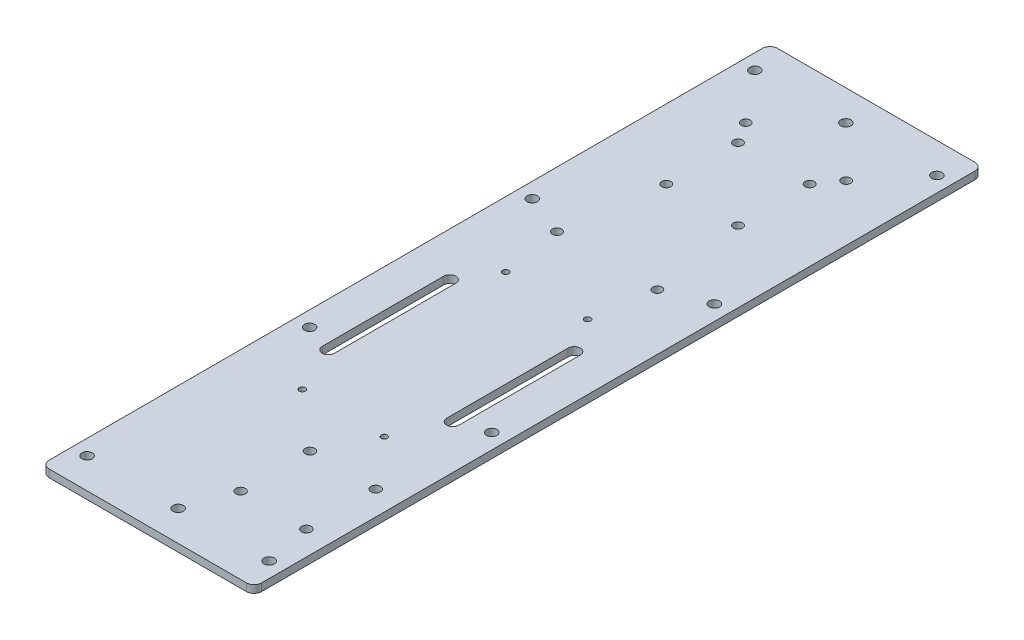
SolidWorks part; units mm, degrees
ref_plane "Front Plane" through (0, 0, 0) normal (0, 0, 1) x (1, 0, 0)
ref_plane "Top Plane" through (0, 0, 0) normal (0, 1, 0) x (1, 0, 0)
ref_plane "Right Plane" through (0, 0, 0) normal (1, 0, 0) x (0, 0, -1)
sketch "Sketch2" plane through (0, 0, 0) normal (0, 1, 0) x (1, 0, 0)
  line L0 (-44.45, 0) -> (44.45, 0) construction
  line L1 (-41.275, 152.4) -> (41.275, 152.4)
  line L2 (-44.45, 149.225) -> (-44.45, -149.225)
  line L3 (-41.275, -152.4) -> (41.275, -152.4)
  line L4 (44.45, 149.225) -> (44.45, -149.225)
  line L5 (0, 152.4) -> (0, -152.4) construction
  arc A0 (-44.45, -149.225) -> (-41.275, -152.4) centre (-41.275, -149.225) ccw
  arc A1 (41.275, -152.4) -> (44.45, -149.225) centre (41.275, -149.225) ccw
  arc A2 (41.275, 152.4) -> (44.45, 149.225) centre (41.275, 149.225) cw
  arc A3 (-41.275, 152.4) -> (-44.45, 149.225) centre (-41.275, 149.225) ccw
  point P8 (0, 0)
  point P13 (-44.45, -152.4)
  point P16 (44.45, -152.4)
  point P21 (-44.45, 152.4)
  dimension "D3" = 3.175
  dimension "D1" = 304.8
  dimension "D2" = 88.9
extrude "Plate Thickness" add sketch "Sketch2" along normal blind 3.175 contours L2 A0 L3 A1 L4 A2 L1 A3
sketch "Sketch3" plane through (0, 3.175, 0) normal (0, 1, 0) x (1, 0, 0)
  line L0 (-44.45, 149.225) -> (-44.45, -149.225) construction
  line L1 (-41.275, 152.4) -> (41.275, 152.4) construction
  line L4 (0, 152.4) -> (0, -152.4) construction
  line L5 (-41.275, -152.4) -> (41.275, -152.4) construction
  line L6 (-41.275, -152.4) -> (41.275, -152.4) construction
  circle A0 centre (-38.1, 139.7) radius 2.159
  circle A1 centre (-38.1, 46.5667) radius 2.159
  circle A2 centre (-38.1, -46.5667) radius 2.159
  circle A3 centre (-38.1, -139.7) radius 2.159
  circle A4 centre (38.1, -139.7) radius 2.159
  circle A5 centre (38.1, -46.5667) radius 2.159
  circle A6 centre (38.1, 46.5667) radius 2.159
  circle A7 centre (38.1, 139.7) radius 2.159
  circle A8 centre (0, 139.7) radius 2.159
  circle A9 centre (0, -139.7) radius 2.159
  dimension "D1" = 4.318
  dimension "D4" = 4.318
  dimension "D2" = 6.35
  dimension "D3" = 12.7
  dimension "D5" = 12.7
  dimension "D6" = 12.7
  dimension "D7" = 93.1333
  dimension "D8" = 93.1333
extrude "Mounting holes" cut sketch "Sketch3" against normal through all
sketch "Sketch4" plane through (0, 3.175, 0) normal (0, 1, 0) x (1, 0, 0)
  line L0 (-21.0058, 39.8143) -> (21.0058, 39.8143) construction
  line L1 (0, 0) -> (0, 139.7) construction
  circle A0 centre (-21.0058, 118.8083) radius 1.905
  circle A1 centre (-21.0058, 39.8143) radius 1.905
  circle A2 centre (21.0058, 39.8143) radius 1.905
  circle A3 centre (21.0058, 118.8083) radius 1.905
  point P13 (0, 39.8143)
  point P17 (0, 69.85)
  point P18 (0, 69.85)
  dimension "D1" = 3.81
  dimension "D2" = 78.994
  dimension "D3" = 42.0116
extrude "Jetson Holes (w/o mount)" cut sketch "Sketch4" against normal through all
sketch "Sketch5" plane through (0, 3.175, 0) normal (0, 1, 0) x (1, 0, 0)
  circle A1 centre (-15.3784, 109.9339) radius 1.905
  circle A3 centre (14.619, 109.9339) radius 1.905
  circle A4 centre (14.619, 79.9365) radius 1.905
  circle A5 centre (-15.3784, 79.9365) radius 1.905
  dimension "D1" = 3.81
  dimension "D2" = 29.9974
  dimension "D3" = 29.9974
extrude "PDB holes" cut sketch "Sketch5" against normal through all
sketch "Sketch6" plane through (0, 3.175, 0) normal (0, 1, 0) x (1, 0, 0)
  circle A6 centre (37.9835, -101.7966) radius 1.905
  circle A7 centre (17.9175, -81.7306) radius 1.905
  circle A8 centre (17.9175, -121.8626) radius 1.905
  dimension "D5" = 3.81
  dimension "D6" = 40.132
  dimension "D7" = 20.066
  dimension "D8" = 20.066
extrude "Lidar Holes" [suppressed] cut sketch "Sketch6" against normal through all
sketch "Sketch7" plane through (0, 3.175, 0) normal (0, 1, 0) x (1, 0, 0)
  line L0 (0, 152.4) -> (0, -152.4) construction
  line L1 (-41.275, 152.4) -> (41.275, 152.4) construction
  line L2 (-41.275, -152.4) -> (41.275, -152.4) construction
  line L3 (17.145, 14.4893) -> (-17.145, 14.4893) construction
  circle A0 centre (-17.145, 14.4893) radius 1.27
  circle A1 centre (-17.145, -70.6007) radius 1.27
  circle A2 centre (17.145, -70.6007) radius 1.27
  circle A3 centre (17.145, 14.4893) radius 1.27
  point P14 (0, 14.4893)
  dimension "D1" = 2.54
  dimension "D2" = 85.09
  dimension "D3" = 34.29
extrude "PixHawk Holes" cut sketch "Sketch7" against normal through all
sketch "Sketch8" plane through (0, 3.175, 0) normal (0, 1, 0) x (1, 0, 0)
  line L0 (0, 152.4) -> (0, -115.5095) construction
  line L1 (-41.275, 152.4) -> (41.275, 152.4) construction
  line L2 (-26.035, -0.006) -> (-26.035, -50.806) construction
  line L3 (-23.495, -0.006) -> (-23.495, -50.806)
  line L4 (-28.575, -0.006) -> (-28.575, -50.806)
  line L5 (26.035, -0.006) -> (26.035, -50.806) construction
  line L6 (23.495, -0.006) -> (23.495, -50.806)
  line L7 (28.575, -0.006) -> (28.575, -50.806)
  arc A0 (-23.495, -0.006) -> (-28.575, -0.006) centre (-26.035, -0.006) ccw
  arc A1 (-28.575, -50.806) -> (-23.495, -50.806) centre (-26.035, -50.806) ccw
  arc A2 (23.495, -0.006) -> (28.575, -0.006) centre (26.035, -0.006) cw
  arc A3 (28.575, -50.806) -> (23.495, -50.806) centre (26.035, -50.806) cw
  point P7 (-26.035, -25.406)
  point P14 (26.035, -25.406)
  dimension "D1" = 50.8
  dimension "D2" = 5.08
  dimension "D3" = 26.035
extrude "Battery Holes" cut sketch "Sketch8" against normal through all
sketch "Sketch9" plane through (0, 3.175, 0) normal (0, 1, 0) x (1, 0, 0)
  circle A0 centre (6.8334, -91.3674) radius 2
  circle A1 centre (34.3334, -91.3674) radius 2
  circle A2 centre (34.3334, -120.3674) radius 2
  circle A3 centre (6.8334, -120.3674) radius 2
  point P8 (0, 0)
  point P9 (10.7904, -94.763)
  point P10 (0, 0)
  point P11 (0, 0)
  point P12 (7.6424, -97.1656)
  point P13 (9.5302, -94.3339)
  point P14 (6.8334, -91.3674)
  dimension "D1" = 4
  dimension "D2" = 27.5
  dimension "D4" = 29
extrude "Cut-Extrude1" cut sketch "Sketch9" against normal through all
